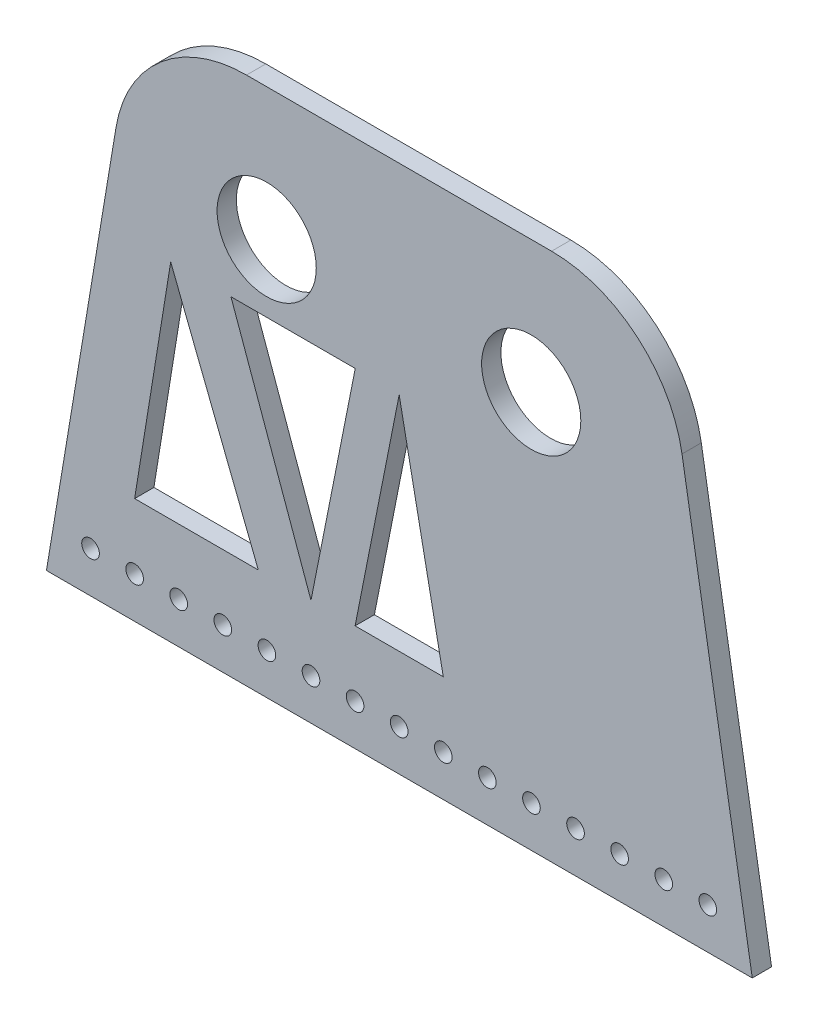
SolidWorks part; units mm, degrees
ref_plane "Front Plane" through (0, 0, 0) normal (0, 0, 1) x (1, 0, 0)
ref_plane "Top Plane" through (0, 0, 0) normal (0, 1, 0) x (1, 0, 0)
ref_plane "Right Plane" through (0, 0, 0) normal (1, 0, 0) x (0, 0, -1)
sketch "Sketch2" plane through (0, 0, 0) normal (0, 0, 1) x (1, 0, 0)
  line L0 (-33.222, -123.0337) -> (-58.5557, -123.0337)
  line L1 (-33.222, 29.3663) -> (119.178, 29.3663)
  line L3 (-33.222, -123.0337) -> (119.178, -123.0337)
  line L5 (-58.5557, -123.0337) -> (-33.222, 29.3663)
  line L6 (119.178, -123.0337) -> (144.7459, -123.0337)
  line L7 (144.7459, -123.0337) -> (119.178, 29.3663)
  line L8 (-22.7678, -28.1678) -> (-33.1557, -92.3946)
  line L9 (-33.1557, -92.3946) -> (2.468, -92.3946)
  line L10 (2.468, -92.3946) -> (-22.7678, -28.1678)
  line L14 (43.0443, -28.3997) -> (55.7443, -92.3946)
  line L15 (55.7443, -92.3946) -> (30.3443, -92.3946)
  line L16 (30.3443, -92.3946) -> (43.0443, -28.3997)
  line L20 (17.6443, -92.3946) -> (30.3903, -28.1678)
  line L21 (30.3903, -28.1678) -> (-5.4154, -28.1678)
  line L22 (-5.4154, -28.1678) -> (17.6443, -92.3946)
  circle A0 centre (4.878, -8.7337) radius 14.2875
  circle A1 centre (81.078, -8.7337) radius 14.2875
  circle A2 centre (-45.8557, -111.1877) radius 2.54
  circle A3 centre (-33.1557, -111.1877) radius 2.54
  circle A4 centre (-20.4557, -111.1877) radius 2.54
  circle A5 centre (-7.7557, -111.1877) radius 2.54
  circle A6 centre (4.9443, -111.1877) radius 2.54
  circle A7 centre (17.6443, -111.1877) radius 2.54
  circle A8 centre (30.3443, -111.1877) radius 2.54
  circle A9 centre (43.0443, -111.1877) radius 2.54
  circle A10 centre (55.7443, -111.1877) radius 2.54
  circle A11 centre (68.4443, -111.1877) radius 2.54
  circle A12 centre (81.1443, -111.1877) radius 2.54
  circle A13 centre (93.8443, -111.1877) radius 2.54
  circle A14 centre (106.5443, -111.1877) radius 2.54
  circle A15 centre (119.2443, -111.1877) radius 2.54
  circle A16 centre (131.9443, -111.1877) radius 2.54
  dimension "D3" = 28.575
  dimension "D4" = 28.575
  dimension "D9" = 15
  dimension "D10" = 12.7
  dimension "D1" = 152.4
  dimension "D2" = 152.4
  dimension "D5" = 76.2
  dimension "D6" = 38.1
  dimension "D7" = 38.1
  dimension "D8" = 38.1
extrude "Boss-Extrude1" add sketch "Sketch2" along normal blind 5.5562
fillet "Fillet1" radius 38.1 2 edges at (-33.222, 29.3663, 2.7781) (119.178, 29.3663, 2.7781)
